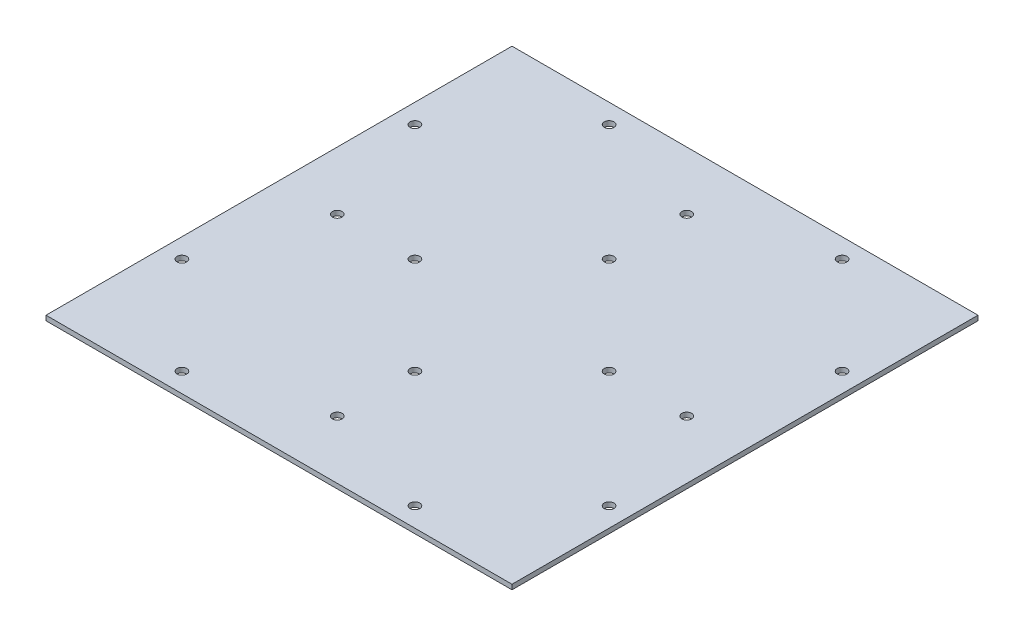
SolidWorks part; units mm, degrees
ref_plane "Front Plane" through (0, 0, 0) normal (0, 0, 1) x (1, 0, 0)
ref_plane "Top Plane" through (0, 0, 0) normal (0, 1, 0) x (1, 0, 0)
ref_plane "Right Plane" through (0, 0, 0) normal (1, 0, 0) x (0, 0, -1)
sketch "Sketch1" plane through (0, 0, 0) normal (0, 1, 0) x (1, 0, 0)
  line L1 (-152.4, 152.4) -> (152.4, 152.4)
  line L2 (-152.4, 152.4) -> (-152.4, -152.4)
  line L3 (-152.4, -152.4) -> (152.4, -152.4)
  line L4 (152.4, 152.4) -> (152.4, -152.4)
  line L5 (-152.4, 152.4) -> (152.4, -152.4) construction
  line L6 (-152.4, -152.4) -> (152.4, 152.4) construction
  point P0 (0, 0)
  dimension "D1" = 304.8
extrude "Boss-Extrude1" add sketch "Sketch1" along normal blind 3.175
sketch "Sketch2" plane through (0, 3.175, 0) normal (0, 1, 0) x (1, 0, 0)
  line L0 (152.4, 152.4) -> (-152.4, 152.4) construction
  circle A0 centre (0, 114.3) radius 3.175
  circle A1 centre (0, 63.5) radius 3.175
  point P6 (0, 152.4)
  dimension "D1" = 6.35
  dimension "D2" = 6.35
  dimension "D3" = 38.1
  dimension "D4" = 50.8
extrude "Cut-Extrude1" cut sketch "Sketch2" against normal up to next
sketch "Sketch3" plane through (0, 3.175, 0) normal (0, 1, 0) x (1, 0, 0)
  point P0 (0, 0)
ref_axis "Axis1" through (0, 3.175, 0) along (0, 1, 0)
pattern_circular "CirPattern1" count 4 over 360 about axis through (0, 3.175, 0) along (0, 1, 0) of "Cut-Extrude1"
sketch "Sketch4" plane through (0, 3.175, 0) normal (0, 1, 0) x (1, 0, 0)
  line L0 (152.4, 152.4) -> (-152.4, 152.4) construction
  line L1 (-76.2, 139.7) -> (76.2, 139.7) construction
  circle A0 centre (-76.2, 139.7) radius 3.175
  circle A1 centre (76.2, 139.7) radius 3.175
  point P8 (0, 139.7)
  dimension "D1" = 6.35
  dimension "D2" = 6.35
  dimension "D3" = 12.7
  dimension "D4" = 152.4
extrude "Cut-Extrude2" cut sketch "Sketch4" against normal up to next
pattern_circular "CirPattern2" count 4 over 360 about axis through (0, 3.175, 0) along (0, 1, 0) of "Cut-Extrude2"
